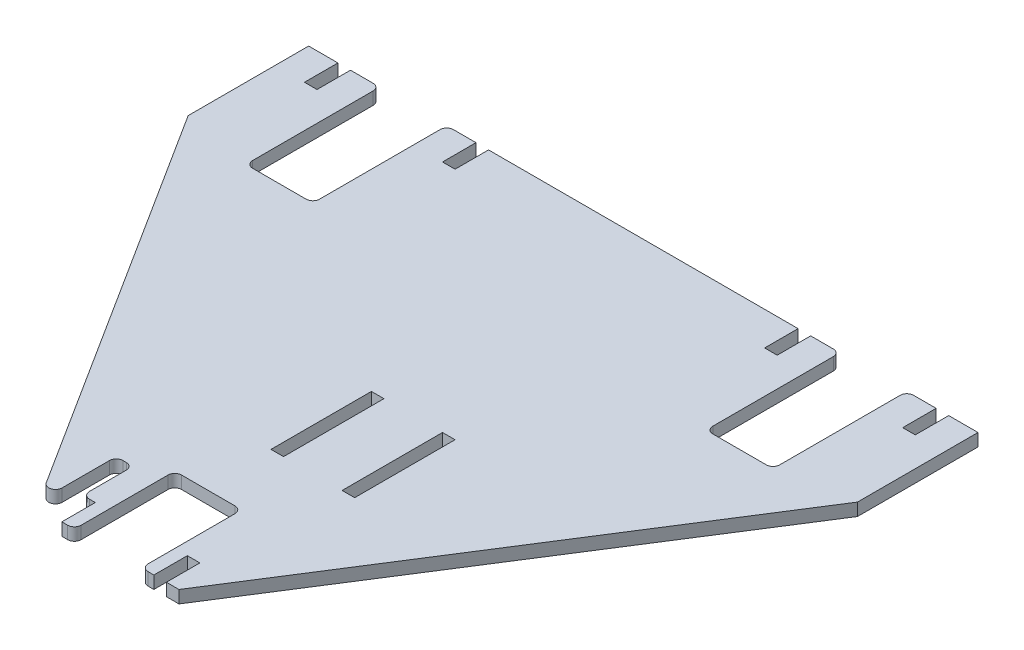
SolidWorks part; units mm, degrees
material "Corrugated Paper"
ref_plane "Front Plane" through (0, 0, 0) normal (0, 0, 1) x (1, 0, 0)
ref_plane "Top Plane" through (0, 0, 0) normal (0, 1, 0) x (1, 0, 0)
ref_plane "Right Plane" through (0, 0, 0) normal (1, 0, 0) x (0, 0, -1)
sketch "Sketch1" plane through (0, 0, 0) normal (0, 1, 0) x (1, 0, 0)
  line L0 (0, 0) -> (0, -142.875) construction
  line L1 (12.7, -63.5) -> (-12.7, -63.5)
  line L2 (-12.7, -63.5) -> (-12.7, -101.6)
  line L3 (-12.7, -101.6) -> (-17.4625, -101.6)
  line L4 (-26.9875, -101.6) -> (-127, 55.88)
  line L5 (-127, 55.88) -> (-127, 101.6)
  line L6 (-127, 101.6) -> (-115.8875, 101.6)
  line L7 (-100.0125, 101.6) -> (-100.0125, 50.8)
  line L9 (-100.0125, 50.8) -> (-74.6125, 50.8)
  line L10 (-74.6125, 50.8) -> (-74.6125, 101.6)
  line L11 (-74.6125, 101.6) -> (-63.5, 101.6)
  line L13 (74.6125, 50.8) -> (74.6125, 101.6)
  line L14 (100.0125, 50.8) -> (74.6125, 50.8)
  line L15 (100.0125, 101.6) -> (100.0125, 50.8)
  line L16 (127, 101.6) -> (115.8875, 101.6)
  line L17 (127, 55.88) -> (127, 101.6)
  line L18 (26.9875, -101.6) -> (127, 55.88)
  line L19 (12.7, -101.6) -> (17.4625, -101.6)
  line L20 (12.7, -63.5) -> (12.7, -101.6)
  line L21 (-127, 101.6) -> (127, -101.6) construction
  line L22 (-22.225, -101.6) -> (-26.9875, -101.6)
  line L24 (-22.225, -101.6) -> (-22.225, -88.9)
  line L25 (-22.225, -88.9) -> (-17.4625, -88.9)
  line L26 (-17.4625, -101.6) -> (-17.4625, -88.9)
  line L27 (22.225, -101.6) -> (22.225, -88.9)
  line L28 (22.225, -88.9) -> (17.4625, -88.9)
  line L29 (17.4625, -101.6) -> (17.4625, -88.9)
  line L30 (22.225, -101.6) -> (26.9875, -101.6)
  line L31 (-87.3125, 50.8) -> (-87.3125, 101.6) construction
  line L32 (-111.125, 101.6) -> (-100.0125, 101.6)
  line L34 (-115.8875, 101.6) -> (-115.8875, 88.9)
  line L35 (-115.8875, 88.9) -> (-111.125, 88.9)
  line L36 (-111.125, 101.6) -> (-111.125, 88.9)
  line L37 (-58.7375, 101.6) -> (-58.7375, 88.9)
  line L38 (-58.7375, 88.9) -> (-63.5, 88.9)
  line L39 (-63.5, 101.6) -> (-63.5, 88.9)
  line L40 (-58.7375, 101.6) -> (58.7375, 101.6)
  line L41 (115.8875, 101.6) -> (115.8875, 88.9)
  line L42 (115.8875, 88.9) -> (111.125, 88.9)
  line L43 (111.125, 101.6) -> (111.125, 88.9)
  line L44 (58.7375, 101.6) -> (58.7375, 88.9)
  line L45 (63.5, 101.6) -> (63.5, 88.9)
  line L46 (58.7375, 88.9) -> (63.5, 88.9)
  line L47 (63.5, 101.6) -> (74.6125, 101.6)
  line L48 (111.125, 101.6) -> (100.0125, 101.6)
  point P26 (0, -63.5)
  dimension "D2" = 25.4
  dimension "D3" = 254
  dimension "D5" = 38.1
  dimension "D6" = 50.8
  dimension "D7" = 203.2
  dimension "D8" = 45.72
  dimension "D9" = 26.9875
  dimension "D4" = 14.2875
  dimension "D10" = 4.7625
  dimension "D11" = 12.7
  dimension "D12" = 4.7625
extrude "Boss-Extrude1" add sketch "Sketch1" along normal blind 4.7625 contours L13 L47 L45 L46 L44 L40 L37 L38 L39 L11 L10 L9 L7 L32 L36 L35 L34 L6 L5 L4 L22 L24 L25 L26 L3 L2 L1 L20 L19 L29 L28 L27 L30 L18 L17 L16 L41 L42 L43 L48 L15 L14
sketch "Sketch2" plane through (0, 4.7625, 0) normal (0, 1, 0) x (1, 0, 0)
  line L0 (14.2875, 0) -> (14.2875, 54.8341) construction
  line L6 (-58.7375, 88.9) -> (-63.5, 88.9) construction
  line L7 (-1.5875, 0) -> (3.175, 0)
  line L8 (-1.5875, 0) -> (-1.5875, -38.1)
  line L9 (-1.5875, -38.1) -> (3.175, -38.1)
  line L10 (3.175, 0) -> (3.175, -38.1)
  line L11 (-22.225, -101.6) -> (-28.575, -101.6)
  line L12 (25.4, 0) -> (25.4, -38.1)
  line L13 (30.1625, -38.1) -> (25.4, -38.1)
  line L14 (30.1625, 0) -> (30.1625, -38.1)
  line L15 (30.1625, 0) -> (25.4, 0)
  line L16 (-22.225, -101.6) -> (-22.225, -69.85)
  line L17 (12.7, -63.5) -> (-12.7, -63.5) construction
  line L18 (-22.225, -69.85) -> (-28.575, -69.85)
  line L19 (-28.575, -101.6) -> (-28.575, -69.85)
  dimension "D2" = 25.4
  dimension "D4" = 14.2875
  dimension "D3" = 31.75
  dimension "D1" = 38.1
  dimension "D5" = 6.35
  dimension "D6" = 31.75
extrude "Cut-Extrude1" cut sketch "Sketch2" against normal through all
ref_plane "Plane1" through (30.1625, 4.7625, 0) normal (-1, 0, 0) x (0, 0, 1)
fillet "Fillet1" radius 2.54 4 edges at (-22.225, 2.3813, 88.9) (-28.575, 2.3813, 99.1003) (-22.225, 2.3813, 69.85) (-28.575, 2.3813, 69.85)
fillet "Fillet2" radius 2.54 12 edges at (-12.7, 2.3813, 101.6) (12.7, 2.3813, 101.6) (12.7, 2.3813, 63.5) (-12.7, 2.3813, 63.5) (100.0125, 2.3813, -101.6) (100.0125, 2.3813, -50.8) (74.6125, 2.3813, -101.6) (74.6125, 2.3813, -50.8) (-100.0125, 2.3813, -101.6) (-74.6125, 2.3813, -101.6) (-74.6125, 2.3813, -50.8) (-100.0125, 2.3813, -50.8)
equation "\"D1@Boss-Extrude1\"=\"thick@FullAssem.Assembly\""
equation "\"D4@Sketch1\"=\"thick@FullAssem.Assembly\"*3"
equation "\"D10@Sketch1\"=\"thick@FullAssem.Assembly\""
equation "\"D9@Sketch1\"=\"thick@FullAssem.Assembly\"*3+0.5"
equation "\"D12@Sketch1\"=\"thick@FullAssem.Assembly\""
equation "\"D3@Sketch2\"=\"MotorLength@Motor-1.Part\""
equation "\"D1@Sketch2\" =  ( \"MotorDiameter@Motor<1>.Part\" + 0.5 ) "
equation "\"D4@Sketch2\"=3*\"thick@FullAssem.Assembly\""
